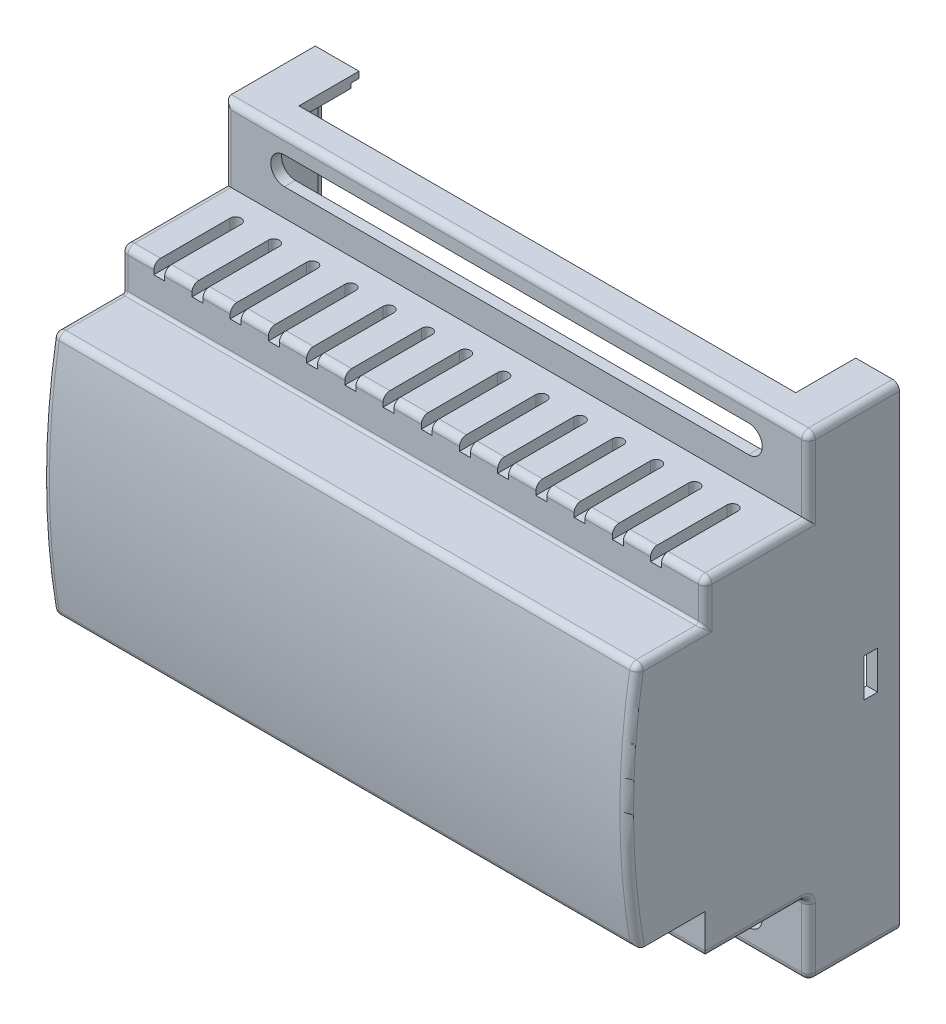
SolidWorks part; units mm, degrees
ref_plane "Alzado" through (0, 0, 0) normal (0, 0, 1) x (1, 0, 0)
ref_plane "Planta" through (0, 0, 0) normal (0, 1, 0) x (1, 0, 0)
ref_plane "Vista lateral" through (0, 0, 0) normal (1, 0, 0) x (0, 0, -1)
sketch "Sketch1" plane through (0, 0, 0) normal (1, 0, 0) x (0, 0, -1)
  line L0 (0, -43.5) -> (0, 43.5)
  line L1 (0, 43.5) -> (-16.65, 43.5)
  line L2 (-16.65, 43.5) -> (-16.65, 30)
  line L3 (-16.65, 30) -> (-35.59, 30)
  line L4 (-35.59, 30) -> (-35.59, 22.5)
  line L5 (-35.59, 22.5) -> (-48, 22.5)
  line L7 (55, 0) -> (-55, 0) construction
  line L8 (-35.59, -22.5) -> (-48, -22.5)
  line L9 (-35.59, -30) -> (-35.59, -22.5)
  line L10 (-16.65, -30) -> (-35.59, -30)
  line L11 (-16.65, -43.5) -> (-16.65, -30)
  line L12 (0, -43.5) -> (-16.65, -43.5)
  arc A1 (-48, 22.5) -> (-48, -22.5) centre (79.6725, 0) ccw
  point P12 (-48, 0)
  point P17 (0, 0)
  dimension "D7" = 259.28
  dimension "D1" = 87
  dimension "D2" = 16.65
  dimension "D3" = 35.59
  dimension "D4" = 48
  dimension "D5" = 60
  dimension "D6" = 45
extrude "Boss-Extrude3" add sketch "Sketch1" along normal blind 107
shell "Shell3" thickness 2 removed face at (53.5, 0, 0)
fillet "Fillet3" radius 1.25 26 edges at (107, 0, 49.9675) (53.5, -22.5, 48) (0, 0, 49.9675) (53.5, 22.5, 48) (107, -36.75, 16.65) (0, -36.75, 16.65) (53.5, -30, 35.59) (107, -30, 26.12) (53.5, -30, 16.65) (0, -30, 26.12) (0, -26.25, 35.59) (0, -22.5, 41.795) (0, 22.5, 41.795) (0, 26.25, 35.59) (0, 30, 26.12) (0, 36.75, 16.65) (53.5, 43.5, 16.65) (107, 43.5, 8.325) (107, 36.75, 16.65) (107, 30, 26.12) (53.5, 30, 35.59) (107, 26.25, 35.59) (107, 22.5, 41.795) (0, -43.5, 8.325) (107, -43.5, 8.325) (53.5, -43.5, 16.65)
sketch "Sketch5" plane through (107, 0, 0) normal (1, 0, 0) x (0, 0, -1)
  line L0 (0, 0) -> (-48.7175, 0) construction
  line L1 (0, -42.25) -> (0, 42.25) construction
  line L2 (-4, 3.5) -> (-6.5, 3.5)
  line L3 (-4, 3.5) -> (-4, -3.5)
  line L4 (-4, -3.5) -> (-6.5, -3.5)
  line L5 (-6.5, 3.5) -> (-6.5, -3.5)
  line L6 (-4, 3.5) -> (-6.5, -3.5) construction
  line L7 (-4, -3.5) -> (-6.5, 3.5) construction
  arc A0 (-46.9467, 21.25) -> (-46.7305, -22.5) centre (79.6725, 0) ccw construction
  point P7 (-5.25, 0)
  point P14 (-5.25, -3.5)
  dimension "D1" = 4
  dimension "D2" = 7
  dimension "D3" = 2.5
extrude "Cut-Extrude3" cut sketch "Sketch5" against normal through all
sketch "Sketch6" plane through (0, -43.5, 0) normal (0, -1, 0) x (1, 0, 0)
  line L0 (105.75, 0) -> (1.25, 0) construction
  line L1 (99, -11) -> (8, -11)
  line L2 (99, -11) -> (99, 11)
  line L3 (99, 11) -> (8, 11)
  line L4 (8, -11) -> (8, 11)
  line L5 (99, -11) -> (8, 11) construction
  line L6 (99, 11) -> (8, -11) construction
  point P0 (53.5, 0)
  dimension "D1" = 91
  dimension "D2" = 11
extrude "Cut-Extrude4" cut sketch "Sketch6" against normal through all
sketch "Sketch7" plane through (0, 0, 16.65) normal (0, 0, 1) x (1, 0, 0)
  line L0 (11, -37.5) -> (96, -37.5) construction
  line L1 (11, -35) -> (96, -35)
  line L2 (11, -40) -> (96, -40)
  line L3 (96, 37.52) -> (11, 37.52) construction
  line L4 (96, 35) -> (11, 35)
  line L5 (96, 40.04) -> (11, 40.04)
  line L6 (53.5, 42.25) -> (53.5, -43.5) construction
  line L7 (105.75, 42.25) -> (1.25, 42.25) construction
  line L8 (105.75, -43.5) -> (1.25, -43.5) construction
  arc A0 (11, -35) -> (11, -40) centre (11, -37.5) ccw
  arc A1 (96, -40) -> (96, -35) centre (96, -37.5) ccw
  arc A2 (96, 35) -> (96, 40.04) centre (96, 37.52) ccw
  arc A3 (11, 40.04) -> (11, 35) centre (11, 37.52) ccw
  point P2 (53.5, -37.5)
  point P10 (53.5, 37.52)
  dimension "D5" = 2.52
  dimension "D6" = 2.5
  dimension "D1" = 85
  dimension "D2" = 35
  dimension "D3" = 85
  dimension "D4" = 35
extrude "Cut-Extrude5" cut sketch "Sketch7" against normal blind 3
fillet "Fillet4" radius 0.5 30 edges at (2, -20.5, 39.9502) (2, -34.75, 14.65) (105, -20.5, 39.9502) (106.6339, 22.1339, 35.2239) (0.3661, 22.1339, 35.2239) (53.5, -20.5, 46.3105) (53.5, 20.5, 46.3105) (53.5, 22.5, 35.59) (53.5, 28, 33.59) (53.5, 28, 14.65) (105, 0, 47.9675) (105, 20.5, 39.9502) (105, 24.25, 33.59) (105, 28, 24.12) (105, 34.75, 14.65) (105, 41.5, 7.325) (2, 41.5, 7.325) (2, 34.75, 14.65) (2, 28, 24.12) (2, 24.25, 33.59) (2, 20.5, 39.9502) (2, 0, 47.9675) (2, -24.25, 33.59) (53.5, -28, 14.65) (105, -34.75, 14.65) (105, -28, 24.12) (105, -24.25, 33.59) (53.5, -28, 33.59) (2, -28, 24.12) (53.5, -20.5, 33.59)
sketch "Sketch8" plane through (0, -30, 0) normal (0, -1, 0) x (1, 0, 0)
  line L0 (107, 35.59) -> (1.25, 35.59) construction
  line L1 (6, 35.59) -> (8, 35.59)
  line L2 (6, 35.59) -> (6, 21.59)
  line L4 (8, 35.59) -> (8, 21.59)
  line L5 (8, 0) -> (1.25, 0) construction
  line L8 (53.5, 49.9675) -> (53.5, 0) construction
  line L9 (105.75, 49.9675) -> (1.25, 49.9675) construction
  line L10 (104.5, 0) -> (99, 0) construction
  line L11 (0, 17.9) -> (0, 34.34) construction
  line L12 (13, 35.59) -> (13, 21.59)
  line L13 (15, 35.59) -> (15, 21.59)
  line L14 (13, 35.59) -> (15, 35.59)
  line L15 (20, 35.59) -> (20, 21.59)
  line L16 (22, 35.59) -> (22, 21.59)
  line L17 (20, 35.59) -> (22, 35.59)
  line L18 (27, 35.59) -> (27, 21.59)
  line L19 (29, 35.59) -> (29, 21.59)
  line L20 (27, 35.59) -> (29, 35.59)
  line L21 (34, 35.59) -> (34, 21.59)
  line L22 (36, 35.59) -> (36, 21.59)
  line L23 (34, 35.59) -> (36, 35.59)
  line L24 (41, 35.59) -> (41, 21.59)
  line L25 (43, 35.59) -> (43, 21.59)
  line L26 (41, 35.59) -> (43, 35.59)
  line L27 (48, 35.59) -> (48, 21.59)
  line L28 (50, 35.59) -> (50, 21.59)
  line L29 (48, 35.59) -> (50, 35.59)
  line L30 (55, 35.59) -> (55, 21.59)
  line L31 (57, 35.59) -> (57, 21.59)
  line L32 (55, 35.59) -> (57, 35.59)
  line L33 (62, 35.59) -> (62, 21.59)
  line L34 (64, 35.59) -> (64, 21.59)
  line L35 (62, 35.59) -> (64, 35.59)
  line L36 (69, 35.59) -> (69, 21.59)
  line L37 (71, 35.59) -> (71, 21.59)
  line L38 (69, 35.59) -> (71, 35.59)
  line L39 (76, 35.59) -> (76, 21.59)
  line L40 (78, 35.59) -> (78, 21.59)
  line L41 (76, 35.59) -> (78, 35.59)
  line L42 (83, 35.59) -> (83, 21.59)
  line L43 (85, 35.59) -> (85, 21.59)
  line L44 (83, 35.59) -> (85, 35.59)
  line L45 (90, 35.59) -> (90, 21.59)
  line L46 (92, 35.59) -> (92, 21.59)
  line L47 (90, 35.59) -> (92, 35.59)
  line L48 (97, 35.59) -> (97, 21.59)
  line L49 (99, 35.59) -> (99, 21.59)
  line L50 (97, 35.59) -> (99, 35.59)
  arc A0 (6, 21.59) -> (8, 21.59) centre (7, 21.59) ccw
  arc A1 (13, 21.59) -> (15, 21.59) centre (14, 21.59) ccw
  arc A2 (20, 21.59) -> (22, 21.59) centre (21, 21.59) ccw
  arc A3 (27, 21.59) -> (29, 21.59) centre (28, 21.59) ccw
  arc A4 (34, 21.59) -> (36, 21.59) centre (35, 21.59) ccw
  arc A5 (41, 21.59) -> (43, 21.59) centre (42, 21.59) ccw
  arc A6 (48, 21.59) -> (50, 21.59) centre (49, 21.59) ccw
  arc A7 (55, 21.59) -> (57, 21.59) centre (56, 21.59) ccw
  arc A8 (62, 21.59) -> (64, 21.59) centre (63, 21.59) ccw
  arc A9 (69, 21.59) -> (71, 21.59) centre (70, 21.59) ccw
  arc A10 (76, 21.59) -> (78, 21.59) centre (77, 21.59) ccw
  arc A11 (83, 21.59) -> (85, 21.59) centre (84, 21.59) ccw
  arc A12 (90, 21.59) -> (92, 21.59) centre (91, 21.59) ccw
  arc A13 (97, 21.59) -> (99, 21.59) centre (98, 21.59) ccw
  point P17 (6, 28.59)
  dimension "D1" = 1
  dimension "D2" = 21.59
  dimension "D3" = 6
  dimension "D4" = 14
extrude "Cut-Extrude7" cut sketch "Sketch8" against normal blind 2
mirror "Mirror1" about plane through (0, 0, 0) normal (0, 1, 0) of "Cut-Extrude7"
sketch "Sketch10" plane through (0, 0, 0) normal (0, 0, -1) x (-1, 0, 0)
  line L8 (-107, -42.25) -> (-107, 42.25) construction
  line L9 (-105.85, 42.35) -> (-1.15, 42.35)
  line L10 (-105.85, 42.35) -> (-105.85, -42.35)
  line L11 (-105.85, -42.35) -> (-1.15, -42.35)
  line L12 (-1.15, 42.35) -> (-1.15, -42.35)
  line L13 (0, -42.25) -> (0, 43.5) construction
  line L14 (-105.75, 43.5) -> (-99, 43.5) construction
  line L15 (-105.75, -43.5) -> (-99, -43.5) construction
  dimension "D1" = 1.15
  dimension "D2" = 1.15
  dimension "D3" = 1.15
  dimension "D4" = 1.15
extrude "Cut-Extrude8" cut sketch "Sketch10" against normal blind 1.5
fillet "Fillet5" radius 0.5 7 edges at (105, -41.5, 7.825) (104.8536, -41.5, 14.5036) (53.5, -41.5, 14.65) (2.1464, -41.5, 14.5036) (1.15, -42.35, 0.75) (2, -41.5, 7.825) (105.85, -42.35, 0.75)
